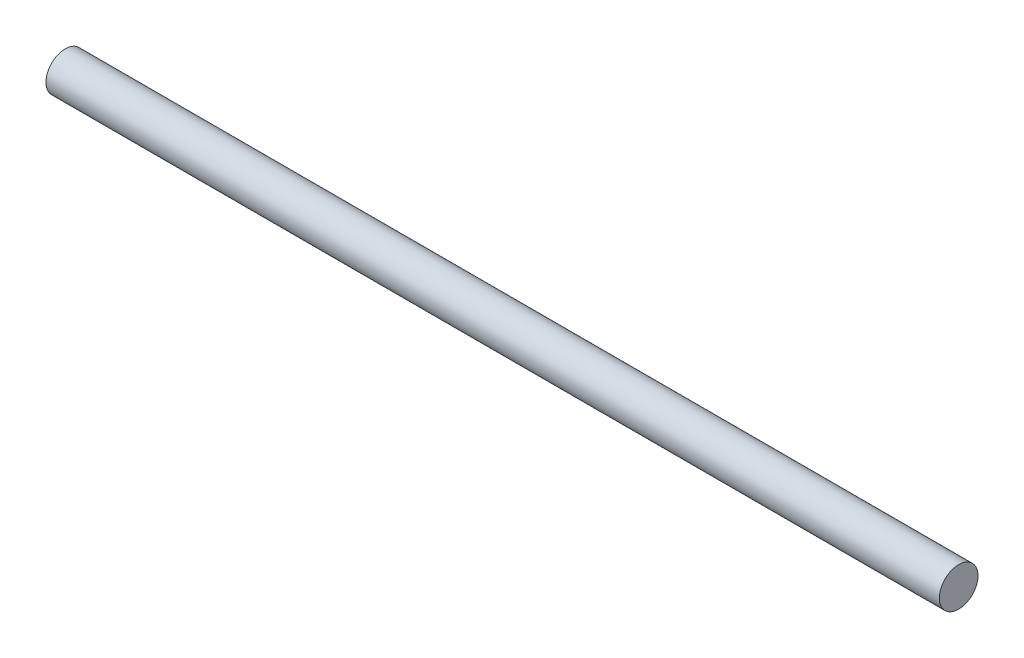
SolidWorks part; units mm, degrees
ref_plane "Alzado" through (0, 0, 0) normal (0, 0, 1) x (1, 0, 0)
ref_plane "Planta" through (0, 0, 0) normal (0, 1, 0) x (1, 0, 0)
ref_plane "Vista lateral" through (0, 0, 0) normal (1, 0, 0) x (0, 0, -1)
sketch "Croquis1" plane through (0, 0, 0) normal (0, 0, 1) x (1, 0, 0)
  line L0 (0, 0) -> (231, 0)
  dimension "D1" = 231
sweep "Barrer1" add path "Croquis1" circular profile diameter 10 parameters "D3"=10
